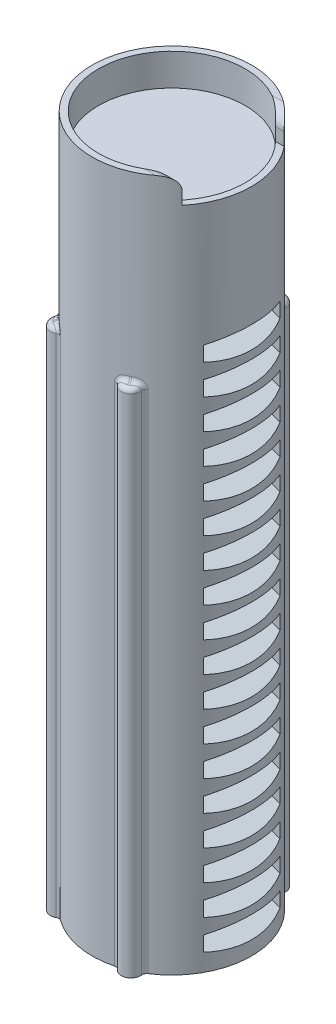
SolidWorks part; units mm, degrees
ref_plane "Front Plane" through (0, 0, 0) normal (0, 0, 1) x (1, 0, 0)
ref_plane "Top Plane" through (0, 0, 0) normal (0, 1, 0) x (1, 0, 0)
ref_plane "Right Plane" through (0, 0, 0) normal (1, 0, 0) x (0, 0, -1)
sketch "Sketch1" plane through (0, 0, 0) normal (0, 1, 0) x (1, 0, 0)
  circle A0 centre (0, 0) radius 12.5
  dimension "D1" = 25
extrude "Boss-Extrude1" add sketch "Sketch1" along normal mid plane 113.5
sketch "Sketch3" plane through (0, 0, 0) normal (0, 0, 1) x (1, 0, 0)
  line L1 (9.125, -52.038) -> (12.5, -50.8095)
  line L3 (12.5, -50.8095) -> (12.5, -54.2575)
  line L4 (12.5, -56.75) -> (9.125, -56.75)
  line L5 (-12.5, -56.75) -> (12.5, -56.75) construction
  line L6 (9.125, -56.75) -> (12.5, -55.5215)
  line L8 (12.5, -56.75) -> (12.5, 56.75) construction
  line L9 (12.5, -55.5215) -> (12.5, -56.75)
  line L10 (12.5, -55.5215) -> (12.5, -54.2575)
  line L13 (12.5, -54.2575) -> (9.125, -53.029)
  line L14 (9.125, -53.029) -> (9.125, -52.038)
  line L15 (12.5, -49.5455) -> (9.125, -48.317)
  line L16 (9.125, -48.317) -> (9.125, -47.326)
  line L17 (9.125, -47.326) -> (12.5, -46.0975)
  line L18 (12.5, -50.8095) -> (12.5, -49.5455)
  line L19 (12.5, -44.8335) -> (9.125, -43.605)
  line L20 (9.125, -43.605) -> (9.125, -42.614)
  line L21 (9.125, -42.614) -> (12.5, -41.3855)
  line L22 (12.5, -46.0975) -> (12.5, -44.8335)
  line L23 (12.5, -40.1215) -> (9.125, -38.893)
  line L24 (9.125, -38.893) -> (9.125, -37.902)
  line L25 (9.125, -37.902) -> (12.5, -36.6735)
  line L26 (12.5, -41.3855) -> (12.5, -40.1215)
  line L27 (12.5, -35.4095) -> (9.125, -34.181)
  line L28 (9.125, -34.181) -> (9.125, -33.19)
  line L29 (9.125, -33.19) -> (12.5, -31.9615)
  line L30 (12.5, -36.6735) -> (12.5, -35.4095)
  line L31 (12.5, -30.6975) -> (9.125, -29.469)
  line L32 (9.125, -29.469) -> (9.125, -28.478)
  line L33 (9.125, -28.478) -> (12.5, -27.2495)
  line L34 (12.5, -31.9615) -> (12.5, -30.6975)
  line L35 (12.5, -25.9855) -> (9.125, -24.757)
  line L36 (9.125, -24.757) -> (9.125, -23.766)
  line L37 (9.125, -23.766) -> (12.5, -22.5375)
  line L38 (12.5, -27.2495) -> (12.5, -25.9855)
  line L39 (12.5, -21.2735) -> (9.125, -20.045)
  line L40 (9.125, -20.045) -> (9.125, -19.054)
  line L41 (9.125, -19.054) -> (12.5, -17.8255)
  line L42 (12.5, -22.5375) -> (12.5, -21.2735)
  line L43 (12.5, -16.5615) -> (9.125, -15.333)
  line L44 (9.125, -15.333) -> (9.125, -14.342)
  line L45 (9.125, -14.342) -> (12.5, -13.1135)
  line L46 (12.5, -17.8255) -> (12.5, -16.5615)
  line L47 (12.5, -11.8495) -> (9.125, -10.621)
  line L48 (9.125, -10.621) -> (9.125, -9.63)
  line L49 (9.125, -9.63) -> (12.5, -8.4015)
  line L50 (12.5, -13.1135) -> (12.5, -11.8495)
  line L51 (12.5, -7.1375) -> (9.125, -5.909)
  line L52 (9.125, -5.909) -> (9.125, -4.918)
  line L53 (9.125, -4.918) -> (12.5, -3.6895)
  line L54 (12.5, -8.4015) -> (12.5, -7.1375)
  line L55 (12.5, -2.4255) -> (9.125, -1.197)
  line L56 (9.125, -1.197) -> (9.125, -0.206)
  line L57 (9.125, -0.206) -> (12.5, 1.0225)
  line L58 (12.5, -3.6895) -> (12.5, -2.4255)
  line L59 (12.5, 2.2865) -> (9.125, 3.515)
  line L60 (9.125, 3.515) -> (9.125, 4.506)
  line L61 (9.125, 4.506) -> (12.5, 5.7345)
  line L62 (12.5, 1.0225) -> (12.5, 2.2865)
  line L63 (12.5, 6.9985) -> (9.125, 8.227)
  line L64 (9.125, 8.227) -> (9.125, 9.218)
  line L65 (9.125, 9.218) -> (12.5, 10.4465)
  line L66 (12.5, 5.7345) -> (12.5, 6.9985)
  line L67 (12.5, 11.7105) -> (9.125, 12.939)
  line L68 (9.125, 12.939) -> (9.125, 13.93)
  line L69 (9.125, 13.93) -> (12.5, 15.1585)
  line L70 (12.5, 10.4465) -> (12.5, 11.7105)
  line L71 (12.5, 16.4225) -> (9.125, 17.651)
  line L72 (9.125, 17.651) -> (9.125, 18.642)
  line L73 (9.125, 18.642) -> (12.5, 19.8705)
  line L74 (12.5, 15.1585) -> (12.5, 16.4225)
  line L75 (12.5, 21.1345) -> (9.125, 22.363)
  line L76 (9.125, 22.363) -> (9.125, 23.354)
  line L77 (9.125, 23.354) -> (12.5, 24.5825)
  line L78 (12.5, 19.8705) -> (12.5, 21.1345)
  line L79 (12.5, 25.8465) -> (9.125, 27.075)
  line L80 (9.125, 27.075) -> (9.125, 28.066)
  line L81 (9.125, 28.066) -> (12.5, 29.2945)
  line L82 (12.5, 24.5825) -> (12.5, 25.8465)
  line L83 (12.5, 30.5585) -> (9.125, 31.787)
  line L84 (9.125, 31.787) -> (9.125, 32.778)
  line L85 (9.125, 32.778) -> (12.5, 34.0065)
  line L86 (12.5, 29.2945) -> (12.5, 30.5585)
  line L91 (12.5, -49.5455) -> (12.5, -46.0975)
  line L92 (12.5, -44.8335) -> (12.5, -41.3855)
  line L93 (12.5, -40.1215) -> (12.5, -36.6735)
  line L94 (12.5, -35.4095) -> (12.5, -31.9615)
  line L95 (12.5, -30.6975) -> (12.5, -27.2495)
  line L96 (12.5, -25.9855) -> (12.5, -22.5375)
  line L97 (12.5, -21.2735) -> (12.5, -17.8255)
  line L98 (12.5, -16.5615) -> (12.5, -13.1135)
  line L99 (12.5, -11.8495) -> (12.5, -8.4015)
  line L100 (12.5, -7.1375) -> (12.5, -3.6895)
  line L101 (12.5, -2.4255) -> (12.5, 1.0225)
  line L102 (12.5, 2.2865) -> (12.5, 5.7345)
  line L103 (12.5, 6.9985) -> (12.5, 10.4465)
  line L104 (12.5, 11.7105) -> (12.5, 15.1585)
  line L105 (12.5, 16.4225) -> (12.5, 19.8705)
  line L106 (12.5, 21.1345) -> (12.5, 24.5825)
  line L107 (12.5, 25.8465) -> (12.5, 29.2945)
  line L108 (12.5, 30.5585) -> (12.5, 34.0065)
  line L125 (9.125, 37.49) -> (12.5, 38.7185) [skipped]
  line L126 (9.125, 36.499) -> (9.125, 37.49) [skipped]
  line L127 (12.5, 35.2705) -> (9.125, 36.499) [skipped]
  line L128 (12.5, 34.0065) -> (12.5, 35.2705) [skipped]
  dimension "D1" = 1.264
  dimension "D2" = 3.721
  dimension "D3" = 3.375
  dimension "D4" = 0.991
  dimension "D5" = 20
extrude "Cut-Extrude1" cut sketch "Sketch3" against normal blind 6 and the other way blind 6 contours L83 L108 L85 L84 | L79 L107 L81 L80 | L75 L106 L77 L76 | L71 L105 L73 L72 | L67 L104 L69 L68 | L63 L103 L65 L64 | L59 L102 L61 L60 | L55 L101 L57 L56 | L51 L100 L53 L52 | L47 L99 L49 L48 | L43 L98 L45 L44 | L39 L97 L41 L40 | L35 L96 L37 L36 | L31 L95 L33 L32 | L27 L94 L29 L28 | L23 L93 L25 L24 | L19 L92 L21 L20 | L15 L91 L17 L16 region at (11.1238, 32.2825, 0) region at (11.1238, 27.5705, 0) region at (11.1238, 22.8585, 0) region at (11.1238, 18.1465, 0) region at (11.1238, 13.4345, 0) region at (11.1238, 8.7225, 0) region at (11.1238, 4.0105, 0) region at (11.1238, -0.7015, 0) region at (11.1238, -5.4135, 0) region at (11.1238, -10.1255, 0) region at (11.1238, -14.8375, 0) region at (11.1238, -19.5495, 0) region at (11.1238, -24.2615, 0) region at (11.1238, -28.9735, 0) region at (11.1238, -33.6855, 0) region at (11.1238, -38.3975, 0) region at (11.1238, -43.1095, 0) region at (11.1238, -47.8215, 0)
sketch "Sketch4" plane through (0, 56.75, 0) normal (0, 1, 0) x (1, 0, 0)
  line L0 (9.6047, 8) -> (8.2614, 8)
  line L1 (9.6047, -8) -> (8.2614, -8)
  arc A0 (8.2614, 8) -> (8.2614, -8) centre (0, 0) ccw
  circle A1 centre (0, 0) radius 12.5 construction
  arc A2 (9.6047, 8) -> (9.6047, -8) centre (0, 0) cw
  dimension "D1" = 1
  dimension "D2" = 16
extrude "Cut-Extrude2" cut sketch "Sketch4" against normal blind 4
sketch "Sketch8" plane through (0, 52.75, 0) normal (0, 1, 0) x (1, 0, 0)
  circle A0 centre (0, 0) radius 11.5
  arc A1 (8.2614, 8) -> (8.2614, -8) centre (0, 0) ccw construction
extrude "Cut-Extrude6" cut sketch "Sketch8" against normal blind 1
fillet "Fillet1" radius 2 2 edges at (8.933, 56.75, -8) (8.933, 56.75, 8)
sketch "Sketch6" plane through (0, -56.75, 0) normal (0, -1, 0) x (1, 0, 0)
  line L0 (0, 3.9005) -> (0, -4.8412) construction
  line L1 (-7.85, -1.6) -> (-4.65, -1.6)
  line L2 (-7.85, -1.6) -> (-7.85, 1.6)
  line L3 (-7.85, 1.6) -> (-4.65, 1.6)
  line L4 (-4.65, -1.6) -> (-4.65, 1.6)
  line L5 (-7.85, -1.6) -> (-4.65, 1.6) construction
  line L6 (-7.85, 1.6) -> (-4.65, -1.6) construction
  line L7 (0, 0) -> (-12.5, 0) construction
  line L8 (7.85, 1.6) -> (4.65, 1.6)
  line L9 (4.65, -1.6) -> (4.65, 1.6)
  line L10 (7.85, -1.6) -> (4.65, -1.6)
  line L11 (7.85, -1.6) -> (7.85, 1.6)
  circle A0 centre (0, 0) radius 12.5 construction
  circle A1 centre (0, 0) radius 12.5
  circle A2 centre (0, 0) radius 2
  point P3 (-6.25, 0)
  point P12 (-6.25, 0)
  circle M8 centre (0, 0) radius 12.5
  dimension "D2" = 4
  dimension "D1" = 3.2
extrude "Cut-Extrude3" cut sketch "Sketch6" against normal blind 5 contours L11 L10 L9 L8 L4 L1 L2 L3 M8 | L1 L4 L3 L2 | L10 L11 L8 L9 | A2 region at (-6.25, -56.75, 0) region at (6.25, -56.75, 0) region at (-12.1464, -56.75, 0) region at (0, -56.75, 0)
extrude "Cut-Extrude4" cut sketch "Sketch6<3>" against normal blind 3.2 from surface contours L1 L4 L3 L2 | L10 L11 L8 L9 region at (-6.25, -56.75, 0) region at (6.25, -56.75, 0) starting at face at (0, -51.75, -12.5)
sketch "Sketch6<3>" plane through (0, -56.75, 0) normal (0, -1, 0) x (1, 0, 0) same geometry as "Sketch6"
extrude "Cut-Extrude5" cut sketch "Sketch6<4>" against normal blind 5 from surface contours A2 region at (0, -56.75, 0) starting at face at (6.25, -51.75, 0)
sketch "Sketch6<4>" plane through (0, -56.75, 0) normal (0, -1, 0) x (1, 0, 0) same geometry as "Sketch6"
sketch "Sketch7" plane through (0, -51.75, 0) normal (0, -1, 0) x (1, 0, 0)
  line L0 (8.8388, 8.8388) -> (-8.8388, -8.8388) construction
  line L1 (-8.8388, 8.8388) -> (8.8388, -8.8388) construction
  line L2 (-8.8388, 8.8388) -> (-8.8388, -8.8388) construction
  line L3 (-8.8388, 8.8388) -> (8.8388, 8.8388) construction
  line L4 (-9.8356, -7.7143) -> (-7.7143, -9.8356) construction
  line L5 (5, 11.4564) -> (5, -11.4564) construction
  line L6 (3.2589, 12.2163) -> (6.7411, 10.6965) construction
  line L7 (-7.7143, 9.8356) -> (-9.8356, 7.7143) construction
  line L8 (1.8749, -12.8204) -> (8.1251, -10.0925) construction
  line L9 (3.5891, -11.9737) -> (6.3386, -10.7737) construction
  line L10 (3.5891, 11.9737) -> (6.3386, 10.7737) construction
  line L11 (0, 0) -> (5.2, 11.9147) construction
  arc A1 (-9.8356, -7.7143) -> (-7.7143, -9.8356) centre (-8.775, -8.775) ccw
  circle A3 centre (0, 0) radius 12.5 construction
  circle A4 centre (0, 0) radius 12.5
  arc A5 (-7.7143, 9.8356) -> (-9.8356, 7.7143) centre (-8.775, 8.775) ccw
  arc A6 (6.3386, -10.7737) -> (3.5891, -11.9737) centre (4.9639, -11.3737) cw
  arc A7 (6.3386, 10.7737) -> (3.5891, 11.9737) centre (4.9639, 11.3737) ccw
  circle A8 centre (0, 0) radius 13 construction
  point P6 (0, 0)
  point P7 (0, 0)
  point P18 (-8.775, 8.775)
  point P19 (5, 11.4564)
  point P20 (-8.775, -8.775)
  point P25 (5, -11.4564)
  dimension "D1" = 1.5
  dimension "D2" = 5
  dimension "D3" = 26
extrude "Boss-Extrude2" add sketch "Sketch7" against normal blind 80 contours A4 A5 | A4 A7 | A6 A4 | A1 region at (-9.248, -51.75, -9.248) region at (-9.248, -51.75, 9.248) region at (5.2315, -51.75, -11.9868) region at (5.2315, -51.75, 11.9868)
fillet "Fillet3" radius 0.7 16 edges at (-7.7143, -11.75, -9.8356) (6.3386, -11.75, -10.7737) (-7.7143, -11.75, 9.8356) (-9.8356, -11.75, 7.7143) (5, 28.25, 11.4564) (-9.8356, 28.25, -9.8356) (-8.8388, 28.25, -8.8388) (5.5639, 28.25, -12.7484) (3.5891, -11.75, -11.9737) (5, 28.25, -11.4564) (-9.8356, -11.75, -7.7143) (-8.8388, 28.25, 8.8388) (-9.8356, 28.25, 9.8356) (5.5639, 28.25, 12.7484) (3.5891, -11.75, 11.9737) (6.3386, -11.75, 10.7737)
fillet "Fillet4" radius 0.5 24 edges at (-7.85, -48.55, 0) (-7.85, -51.75, 0) (-6.25, -48.55, 1.6) (-7.85, -50.15, 1.6) (-6.25, -51.75, 1.6) (-4.65, -48.55, 0) (-4.65, -50.15, 1.6) (-4.65, -51.75, 0) (-7.85, -50.15, -1.6) (-6.25, -48.55, -1.6) (-4.65, -50.15, -1.6) (-6.25, -51.75, -1.6) (6.25, -48.55, -1.6) (6.25, -51.75, -1.6) (6.25, -48.55, 1.6) (6.25, -51.75, 1.6) (4.65, -50.15, 1.6) (4.65, -48.55, 0) (4.65, -50.15, -1.6) (4.65, -51.75, 0) (7.85, -50.15, -1.6) (7.85, -48.55, 0) (7.85, -50.15, 1.6) (7.85, -51.75, 0)
fillet "Fillet5" radius 0.2 1 edges at (0, -51.75, -2)
